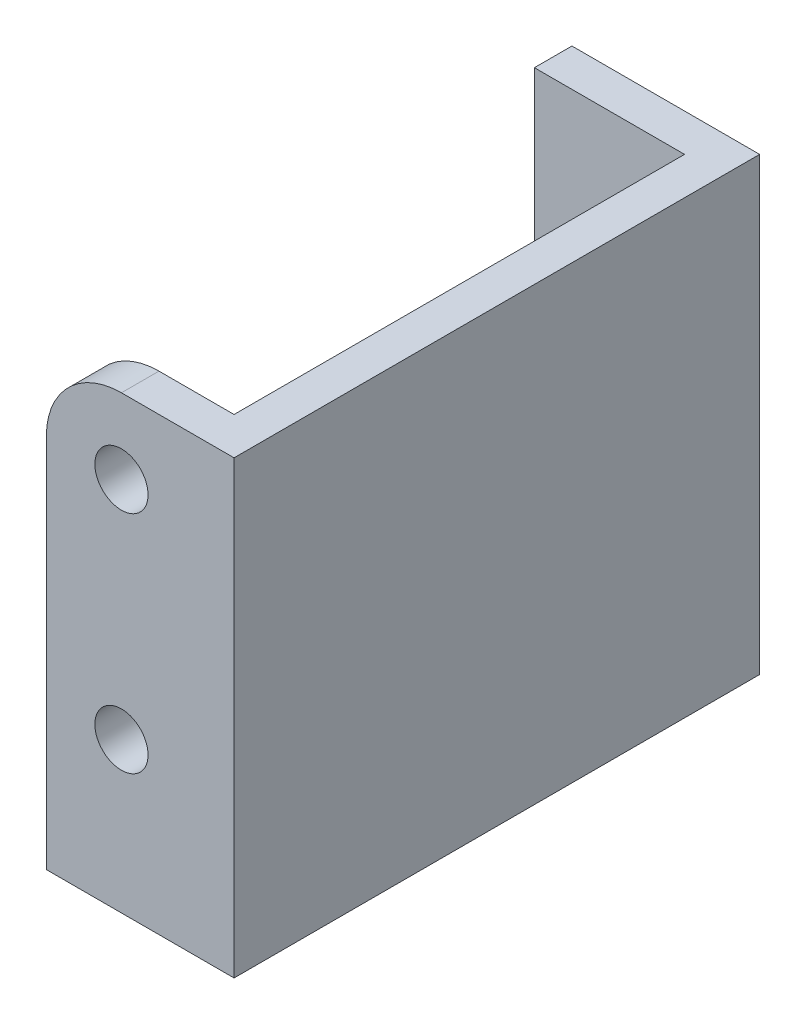
SolidWorks part; units mm, degrees
material "PET"
ref_plane "Front Plane" through (0, 0, 0) normal (0, 0, 1) x (1, 0, 0)
ref_plane "Top Plane" through (0, 0, 0) normal (0, 1, 0) x (1, 0, 0)
ref_plane "Right Plane" through (0, 0, 0) normal (1, 0, 0) x (0, 0, -1)
sketch "Sketch1" plane through (0, 0, 0) normal (0, 0, 1) x (1, 0, 0)
  line L1 (-7.9375, 19.05) -> (7.9375, 19.05)
  line L2 (-7.9375, 19.05) -> (-7.9375, -19.05)
  line L3 (-7.9375, -19.05) -> (7.9375, -19.05)
  line L4 (7.9375, 19.05) -> (7.9375, -19.05)
  line L5 (-7.9375, 19.05) -> (7.9375, -19.05) construction
  line L6 (-7.9375, -19.05) -> (7.9375, 19.05) construction
  point P0 (0, 0)
  dimension "D1" = 38.1
  dimension "D2" = 15.875
extrude "Boss-Extrude1" add sketch "Sketch1" against normal blind 44.45
shell "Shell1" thickness 3.175 removed face at (0, 19.05, -22.225) removed face at (-7.9375, 0, -22.225)
sketch "Sketch2" plane through (0, 0, 0) normal (0, 0, 1) x (1, 0, 0)
  line L0 (7.9375, 19.05) -> (-7.9375, 19.05) construction
  line L1 (-7.9375, 19.05) -> (-7.9375, -19.05) construction
  circle A0 centre (-1.5875, -6.35) radius 2.2479
  circle A1 centre (-1.5875, 12.7) radius 2.2479
  dimension "D1" = 4.4958
  dimension "D2" = 19.05
  dimension "D3" = 6.35
  dimension "D4" = 6.35
extrude "Cut-Extrude1" cut sketch "Sketch2" against normal up to next
fillet "Fillet2" radius 6.35 1 edges at (-7.9375, 19.05, -1.5875)
